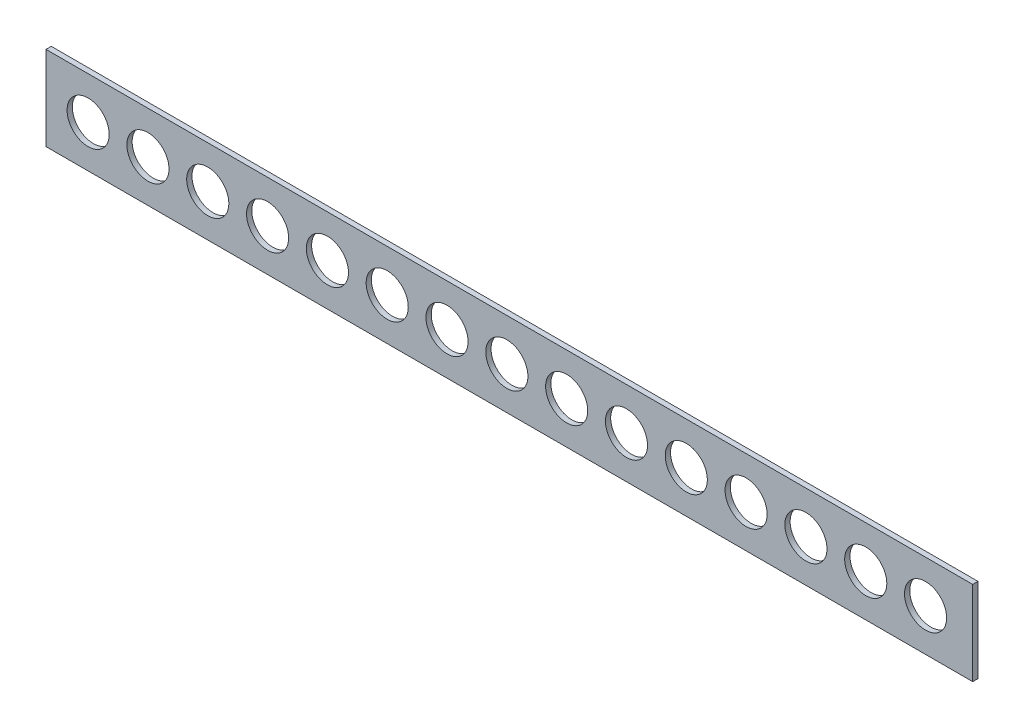
SolidWorks part; units mm, degrees
ref_plane "Front Plane" through (0, 0, 0) normal (0, 0, 1) x (1, 0, 0)
ref_plane "Top Plane" through (0, 0, 0) normal (0, 1, 0) x (1, 0, 0)
ref_plane "Right Plane" through (0, 0, 0) normal (1, 0, 0) x (0, 0, -1)
sketch "Sketch1" plane through (0, 0, 0) normal (0, 0, 1) x (1, 0, 0)
  line L0 (0, 0) -> (0, 50.8)
  line L1 (0, 50.8) -> (558.8, 50.8)
  line L2 (558.8, 50.8) -> (558.8, 0)
  line L3 (558.8, 0) -> (0, 0)
  dimension "D1" = 558.8
  dimension "D2" = 50.8
extrude "Boss-Extrude1" add sketch "Sketch1" along normal blind 3.175
sketch "Sketch2" plane through (0, 0, 3.175) normal (0, 0, 1) x (1, 0, 0)
  line L0 (558.8, 50.8) -> (0, 50.8) construction
  line L2 (0, 50.8) -> (0, 0) construction
  circle A0 centre (25.4, 25.4) radius 12.7
  dimension "D1" = 25.4
  dimension "D3" = 25.4
  dimension "D4" = 25.4
  dimension "D2" = 25.4
extrude "Cut-Extrude1" cut sketch "Sketch2" against normal through all
pattern_linear "LPattern1" count 15 spacing 36.068 along (1, 0, 0) of "Cut-Extrude1"
